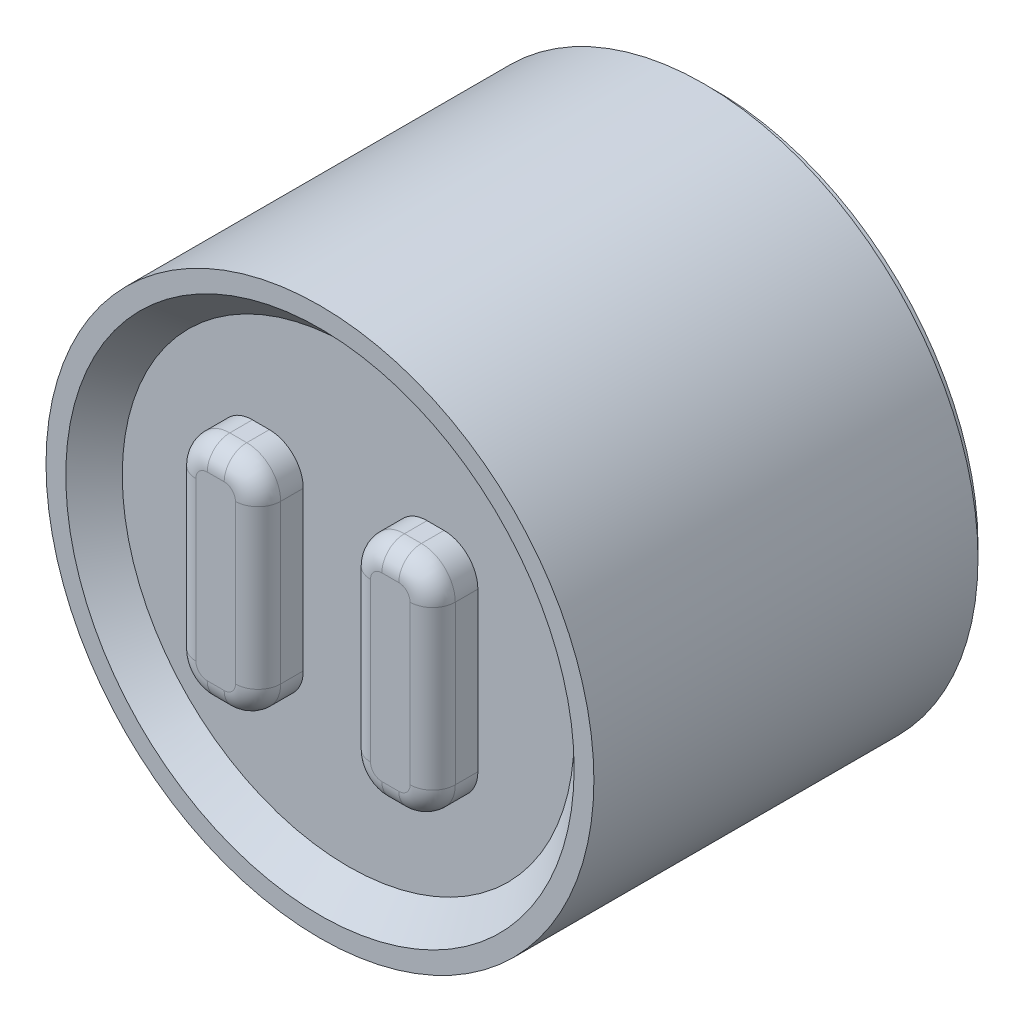
SolidWorks part; units mm, degrees
ref_plane "Спереди" through (0, 0, 0) normal (0, 0, 1) x (1, 0, 0)
ref_plane "Сверху" through (0, 0, 0) normal (0, 1, 0) x (1, 0, 0)
ref_plane "Справа" through (0, 0, 0) normal (1, 0, 0) x (0, 0, -1)
sketch "Эскиз1" plane through (0, 0, 0) normal (0, 0, 1) x (1, 0, 0)
  circle A0 centre (0, 0) radius 4.85
extrude "Бобышка-Вытянуть1" add sketch "Эскиз1" along normal blind 6.8
sketch "Эскиз2" plane through (0, 0, 6.8) normal (0, 0, 1) x (1, 0, 0)
  circle A0 centre (0, 0) radius 4
extrude "Вырез-Вытянуть1" cut sketch "Эскиз2" against normal blind 0.5
chamfer "Фаска1" distance 0.5 angle 45 1 edges at (4, 0, 6.8)
sketch "Эскиз3" plane through (0, 0, 6.3) normal (0, 0, 1) x (1, 0, 0)
  line L0 (0, 3.78) -> (0, -2.8609) construction
  line L1 (-1.6958, 2) -> (-1.3958, 2)
  line L2 (-2.2958, 1.4) -> (-2.2958, -1.4)
  line L3 (-1.6958, -2) -> (-1.3958, -2)
  line L4 (-0.7958, 1.4) -> (-0.7958, -1.4)
  line L5 (-2.2958, 2) -> (-0.7958, -2) construction
  line L6 (-2.2958, -2) -> (-0.7958, 2) construction
  line L7 (2.2958, -2) -> (0.7958, 2) construction
  line L8 (2.2958, 2) -> (0.7958, -2) construction
  line L9 (0.7958, 1.4) -> (0.7958, -1.4)
  line L10 (1.6958, -2) -> (1.3958, -2)
  line L11 (2.2958, 1.4) -> (2.2958, -1.4)
  line L12 (1.6958, 2) -> (1.3958, 2)
  arc A0 (-2.2958, -1.4) -> (-1.6958, -2) centre (-1.6958, -1.4) ccw
  arc A1 (-1.3958, -2) -> (-0.7958, -1.4) centre (-1.3958, -1.4) ccw
  arc A2 (-1.3958, 2) -> (-0.7958, 1.4) centre (-1.3958, 1.4) cw
  arc A3 (-1.6958, 2) -> (-2.2958, 1.4) centre (-1.6958, 1.4) ccw
  arc A4 (1.6958, 2) -> (2.2958, 1.4) centre (1.6958, 1.4) cw
  arc A5 (1.3958, 2) -> (0.7958, 1.4) centre (1.3958, 1.4) ccw
  arc A6 (1.3958, -2) -> (0.7958, -1.4) centre (1.3958, -1.4) cw
  arc A7 (2.2958, -1.4) -> (1.6958, -2) centre (1.6958, -1.4) cw
  point P0 (-1.5458, 0)
  point P36 (1.5458, 0)
  dimension "D3" = 0.6
  dimension "D1" = 4
  dimension "D2" = 1.5
extrude "Бобышка-Вытянуть2" add sketch "Эскиз3" along normal blind 0.8
fillet "Скругление1" radius 0.4 16 edges at (2.2958, 0, 7.1) (2.12, -1.8243, 7.1) (1.5458, -2, 7.1) (0.9715, -1.8243, 7.1) (0.7958, 0, 7.1) (0.9715, 1.8243, 7.1) (1.5458, 2, 7.1) (-0.7958, 0, 7.1) (-0.9715, -1.8243, 7.1) (-1.5458, -2, 7.1) (-2.12, -1.8243, 7.1) (-2.2958, 0, 7.1) (-2.12, 1.8243, 7.1) (-1.5458, 2, 7.1) (2.12, 1.8243, 7.1) (-0.9715, 1.8243, 7.1)
sketch "Эскиз4" plane through (0, 0, 0) normal (0, 0, -1) x (-1, 0, 0)
  circle A0 centre (0, 0) radius 4.65
extrude "Бобышка-Вытянуть3" add sketch "Эскиз4" along normal blind 0.2
